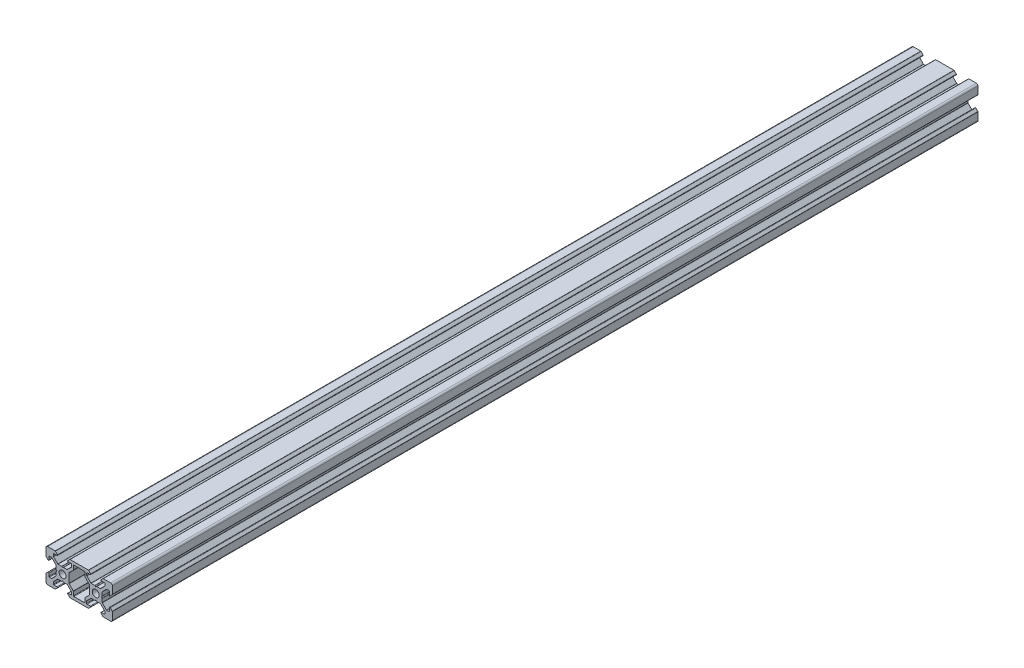
SolidWorks part; units mm, degrees
material "АД31Т ГОСТ 4784-97"
ref_plane "Спереди" through (0, 0, 0) normal (0, 0, 1) x (1, 0, 0)
ref_plane "Сверху" through (0, 0, 0) normal (0, 1, 0) x (1, 0, 0)
ref_plane "Справа" through (0, 0, 0) normal (1, 0, 0) x (0, 0, -1)
sketch "Эскиз1" plane through (0, 0, 0) normal (0, 0, 1) x (1, 0, 0)
  line L0 (12.9654, 0) -> (-12.9654, 0) construction
  line L1 (0, -12.9654) -> (0, 12.9654) construction
  line L2 (0, 0) -> (-18.3359, -18.3359) construction
  line L3 (-10, -10) -> (-10, -4.4)
  line L4 (-10, -4.4) -> (-8.2, -2.6)
  line L5 (-8.2, -2.6) -> (-8.2, -5.4993)
  line L6 (-8.2, -5.4993) -> (-6.56, -5.4993)
  line L7 (-6.56, -5.4993) -> (-3.9007, -2.84)
  line L8 (-3.9007, -2.84) -> (-3.9007, -0.5)
  line L9 (-3.9007, -0.5) -> (-3.4007, 0)
  line L10 (-0.5, -3.9007) -> (0, -3.4007)
  line L11 (-2.84, -3.9007) -> (-0.5, -3.9007)
  line L12 (-5.4993, -6.56) -> (-2.84, -3.9007)
  line L13 (-5.4993, -8.2) -> (-5.4993, -6.56)
  line L14 (-2.6, -8.2) -> (-5.4993, -8.2)
  line L15 (-4.4, -10) -> (-2.6, -8.2)
  line L16 (-10, -10) -> (-4.4, -10)
  line L17 (-10, 10) -> (-4.4, 10)
  line L18 (-4.4, 10) -> (-2.6, 8.2)
  line L19 (-2.6, 8.2) -> (-5.4993, 8.2)
  line L20 (-5.4993, 8.2) -> (-5.4993, 6.56)
  line L21 (-5.4993, 6.56) -> (-2.84, 3.9007)
  line L22 (-2.84, 3.9007) -> (-0.5, 3.9007)
  line L23 (-0.5, 3.9007) -> (0, 3.4007)
  line L24 (-3.9007, 0.5) -> (-3.4007, 0)
  line L25 (-3.9007, 2.84) -> (-3.9007, 0.5)
  line L26 (-6.56, 5.4993) -> (-3.9007, 2.84)
  line L27 (-8.2, 5.4993) -> (-6.56, 5.4993)
  line L28 (-8.2, 2.6) -> (-8.2, 5.4993)
  line L29 (-10, 4.4) -> (-8.2, 2.6)
  line L30 (-10, 10) -> (-10, 4.4)
  line L31 (0.5, 3.9007) -> (0, 3.4007)
  line L32 (0.5, -3.9007) -> (0, -3.4007)
  line L33 (10, -10) -> (10, 10) construction
  line L34 (3.9007, -0.5) -> (3.9007, 0.5)
  line L35 (6.56, -5.4993) -> (6.56, -8.2)
  line L36 (13.44, -5.4993) -> (16.0993, -2.84)
  line L37 (6.56, 5.4993) -> (3.9007, 2.84)
  line L38 (3.9007, 2.84) -> (3.9007, 0.5)
  line L39 (6.56, -8.2) -> (13.44, -8.2)
  line L40 (2.84, 3.9007) -> (0.5, 3.9007)
  line L41 (5.4993, 6.56) -> (2.84, 3.9007)
  line L42 (5.4993, 8.2) -> (5.4993, 6.56)
  line L43 (2.6, 8.2) -> (5.4993, 8.2)
  line L44 (4.4, 10) -> (2.6, 8.2)
  line L45 (15.6, 10) -> (4.4, 10)
  line L46 (15.6, -10) -> (4.4, -10)
  line L47 (4.4, -10) -> (2.6, -8.2)
  line L48 (2.6, -8.2) -> (5.4993, -8.2)
  line L49 (5.4993, -8.2) -> (5.4993, -6.56)
  line L50 (5.4993, -6.56) -> (2.84, -3.9007)
  line L51 (2.84, -3.9007) -> (0.5, -3.9007)
  line L52 (6.56, 5.4993) -> (6.56, 8.2)
  line L53 (3.9007, -2.84) -> (3.9007, -0.5)
  line L54 (6.56, -5.4993) -> (3.9007, -2.84)
  line L55 (16.0993, -2.84) -> (16.0993, -0.5)
  line L56 (6.56, 8.2) -> (13.44, 8.2)
  line L57 (13.44, 5.4993) -> (13.44, 8.2)
  line L58 (17.16, -3.9007) -> (19.5, -3.9007)
  line L59 (14.5007, -6.56) -> (17.16, -3.9007)
  line L60 (14.5007, -8.2) -> (14.5007, -6.56)
  line L61 (17.4, -8.2) -> (14.5007, -8.2)
  line L62 (15.6, -10) -> (17.4, -8.2)
  line L63 (15.6, 10) -> (17.4, 8.2)
  line L64 (17.4, 8.2) -> (14.5007, 8.2)
  line L65 (14.5007, 8.2) -> (14.5007, 6.56)
  line L66 (14.5007, 6.56) -> (17.16, 3.9007)
  line L67 (17.16, 3.9007) -> (19.5, 3.9007)
  line L68 (16.0993, 2.84) -> (16.0993, 0.5)
  line L69 (13.44, 5.4993) -> (16.0993, 2.84)
  line L70 (13.44, -5.4993) -> (13.44, -8.2)
  line L71 (16.0993, -0.5) -> (16.0993, 0.5)
  line L72 (19.5, -3.9007) -> (20, -3.4007)
  line L73 (19.5, 3.9007) -> (20, 3.4007)
  line L74 (30, 10) -> (30, 4.4)
  line L75 (30, 4.4) -> (28.2, 2.6)
  line L76 (28.2, 2.6) -> (28.2, 5.4993)
  line L77 (28.2, 5.4993) -> (26.56, 5.4993)
  line L78 (26.56, 5.4993) -> (23.9007, 2.84)
  line L79 (23.9007, 2.84) -> (23.9007, 0.5)
  line L80 (23.9007, 0.5) -> (23.4007, 0)
  line L81 (20.5, 3.9007) -> (20, 3.4007)
  line L82 (22.84, 3.9007) -> (20.5, 3.9007)
  line L83 (25.4993, 6.56) -> (22.84, 3.9007)
  line L84 (25.4993, 8.2) -> (25.4993, 6.56)
  line L85 (22.6, 8.2) -> (25.4993, 8.2)
  line L86 (24.4, 10) -> (22.6, 8.2)
  line L87 (30, 10) -> (24.4, 10)
  line L88 (30, -10) -> (24.4, -10)
  line L89 (24.4, -10) -> (22.6, -8.2)
  line L90 (22.6, -8.2) -> (25.4993, -8.2)
  line L91 (25.4993, -8.2) -> (25.4993, -6.56)
  line L92 (25.4993, -6.56) -> (22.84, -3.9007)
  line L93 (22.84, -3.9007) -> (20.5, -3.9007)
  line L94 (20.5, -3.9007) -> (20, -3.4007)
  line L95 (23.9007, -0.5) -> (23.4007, 0)
  line L96 (23.9007, -2.84) -> (23.9007, -0.5)
  line L97 (26.56, -5.4993) -> (23.9007, -2.84)
  line L98 (28.2, -5.4993) -> (26.56, -5.4993)
  line L99 (28.2, -2.6) -> (28.2, -5.4993)
  line L100 (30, -4.4) -> (28.2, -2.6)
  line L101 (30, -10) -> (30, -4.4)
  circle A0 centre (0, 0) radius 2.1
  circle A1 centre (20, 0) radius 2.1
  point P62 (10, 8.2)
  point P80 (10, -8.2)
  dimension "D5" = 2.6
  dimension "D10" = 4.2
  dimension "D2" = 10
  dimension "D3" = 1.64
  dimension "D4" = 1.5
  dimension "D6" = 1.8
  dimension "D7" = 2.84
  dimension "D8" = 0.5
  dimension "D9" = 45
extrude "Бобышка-Вытянуть1" add sketch "Эскиз1" along normal blind 522
fillet "Скругление1" radius 1 4 edges at (-10, 10, 261) (-10, -10, 261) (30, 10, 261) (30, -10, 261)
fillet "Скругление2" radius 0.3 83 edges at (-4.4, 10, 261) (-2.6, 8.2, 261) (-5.4993, 8.2, 261) (-5.4993, 6.56, 261) (-2.84, 3.9007, 261) (-0.5, 3.9007, 261) (0.5, 3.9007, 261) (2.84, 3.9007, 261) (5.4993, 6.56, 261) (4.4, 10, 261) (5.4993, 8.2, 261) (2.6, 8.2, 261) (3.9007, 2.84, 261) (3.9007, -2.84, 261) (4.4, -10, 261) (2.6, -8.2, 261) (5.4993, -8.2, 261) (5.4993, -6.56, 261) (2.84, -3.9007, 261) (0.5, -3.9007, 261) (-0.5, -3.9007, 261) (-2.84, -3.9007, 261) (-5.4993, -6.56, 261) (-5.4993, -8.2, 261) (-2.6, -8.2, 261) (-10, -4.4, 261) (-8.2, -2.6, 261) (-8.2, -5.4993, 261) (-6.56, -5.4993, 261) (-3.9007, -2.84, 261) (-3.9007, -0.5, 261) (-3.9007, 0.5, 261) (-3.9007, 2.84, 261) (-6.56, 5.4993, 261) (-8.2, 5.4993, 261) (-8.2, 2.6, 261) (-10, 4.4, 261) (6.56, -5.4993, 261) (6.56, 5.4993, 261) (6.56, 8.2, 261) (13.44, 8.2, 261) (13.44, 5.4993, 261) (16.0993, 2.84, 261) (16.0993, -2.84, 261) (13.44, -5.4993, 261) (13.44, -8.2, 261) (6.56, -8.2, 261) (15.6, 10, 261) (17.4, 8.2, 261) (14.5007, 8.2, 261) (14.5007, 6.56, 261) (17.16, 3.9007, 261) (19.5, 3.9007, 261) (20.5, 3.9007, 261) (22.84, 3.9007, 261) (25.4993, 6.56, 261) (25.4993, 8.2, 261) (22.6, 8.2, 261) (24.4, 10, 261) (30, 4.4, 261) (28.2, 2.6, 261) (28.2, 5.4993, 261) (26.56, 5.4993, 261) (23.9007, 2.84, 261) (23.9007, 0.5, 261) (23.9007, -0.5, 261) (23.9007, -2.84, 261) (26.56, -5.4993, 261) (28.2, -5.4993, 261) (28.2, -2.6, 261) (30, -4.4, 261) (24.4, -10, 261) (22.6, -8.2, 261) (25.4993, -8.2, 261) (25.4993, -6.56, 261) (22.84, -3.9007, 261) (20.5, -3.9007, 261) (19.5, -3.9007, 261) (17.16, -3.9007, 261) (14.5007, -6.56, 261) (14.5007, -8.2, 261) (17.4, -8.2, 261) (15.6, -10, 261)
